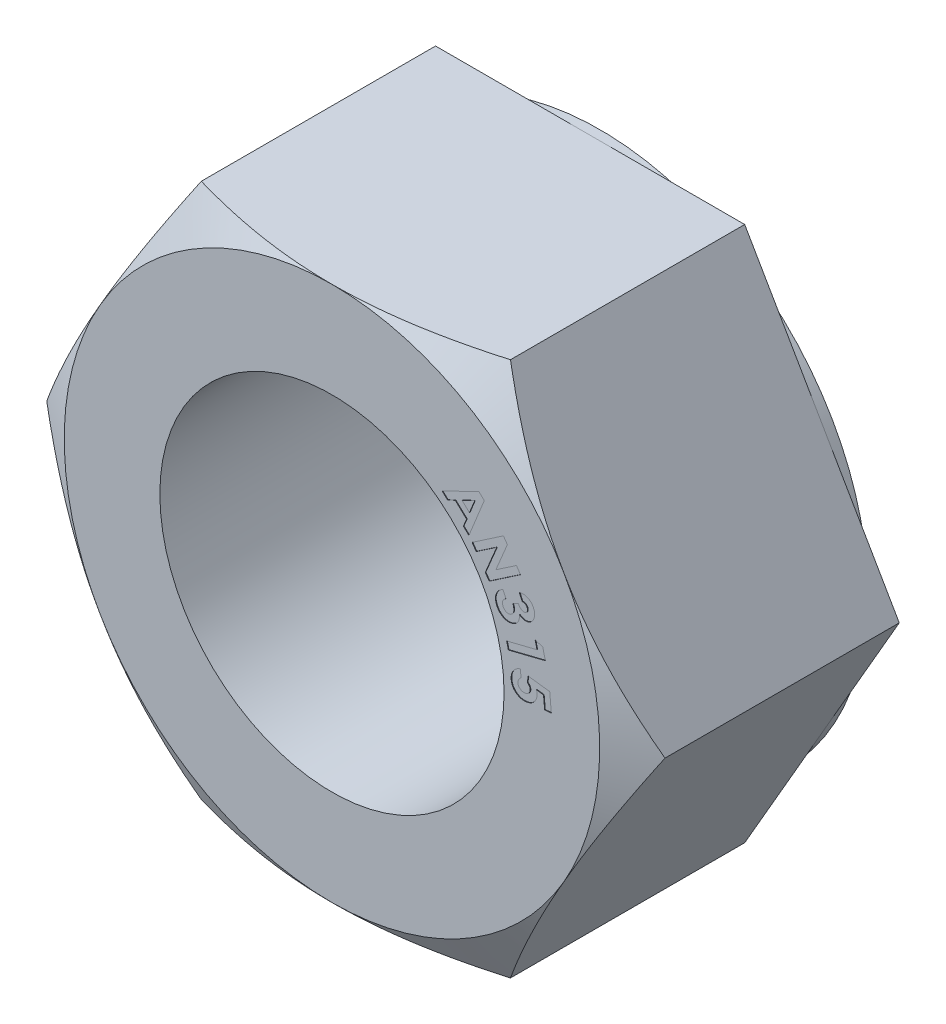
SolidWorks part; units mm, degrees
material "AISI 4340 Steel, normalized"
ref_plane "Front Plane" through (0, 0, 0) normal (0, 0, 1) x (1, 0, 0)
ref_plane "Top Plane" through (0, 0, 0) normal (0, 1, 0) x (1, 0, 0)
ref_plane "Right Plane" through (0, 0, 0) normal (1, 0, 0) x (0, 0, -1)
sketch "Sketch1" plane through (0, 0, 0) normal (0, 0, 1) x (1, 0, 0)
  line L1 (6.4158, 11.1125) -> (-6.4158, 11.1125)
  line L2 (-6.4158, 11.1125) -> (-12.8316, 0)
  line L3 (-12.8316, 0) -> (-6.4158, -11.1125)
  line L4 (-6.4158, -11.1125) -> (6.4158, -11.1125)
  line L5 (6.4158, -11.1125) -> (12.8316, 0)
  line L6 (12.8316, 0) -> (6.4158, 11.1125)
  circle A0 centre (0, 0) radius 11.1125 construction
  circle A1 centre (0, 0) radius 7.1438
  dimension "Diameter A" = 22.225
  dimension "T - Thread" = 14.2875
extrude "Boss-Extrude1" add sketch "Sketch1" along normal blind 10.7156
sketch "Sketch2" plane through (0, 0, 10.7156) normal (0, 0, 1) x (1, 0, 0)
  line L0 (12.8316, 0) -> (6.4158, 11.1125) construction
  circle A0 centre (0, 0) radius 11.1125
extrude "Cut-Extrude1" cut sketch "Sketch2" against normal blind 3.5719 draft 60 flip side to cut
sketch "Sketch3" plane through (0, 0, 0) normal (0, 0, -1) x (-1, 0, 0)
  line L0 (-12.8316, 0) -> (-6.4158, 11.1125) construction
  circle A0 centre (0, 0) radius 11.1125
  circle A1 centre (0, 0) radius 7.1438
  circle A2 centre (0, 0) radius 7.1438 construction
extrude "Boss-Extrude2" add sketch "Sketch3" along normal blind 0.4064
sketch "Sketch4" plane through (0, 0, 10.7156) normal (0, 0, 1) x (1, 0, 0)
  circle A0 centre (0, 0) radius 7.5248 construction
  circle A1 centre (0, 0) radius 7.1438 construction
  text T0 "AN315" font "Century Gothic" height in points 6
  dimension "D1" = 0.381
extrude "Cut-Extrude2" cut sketch "Sketch4" against normal blind 0.0254
